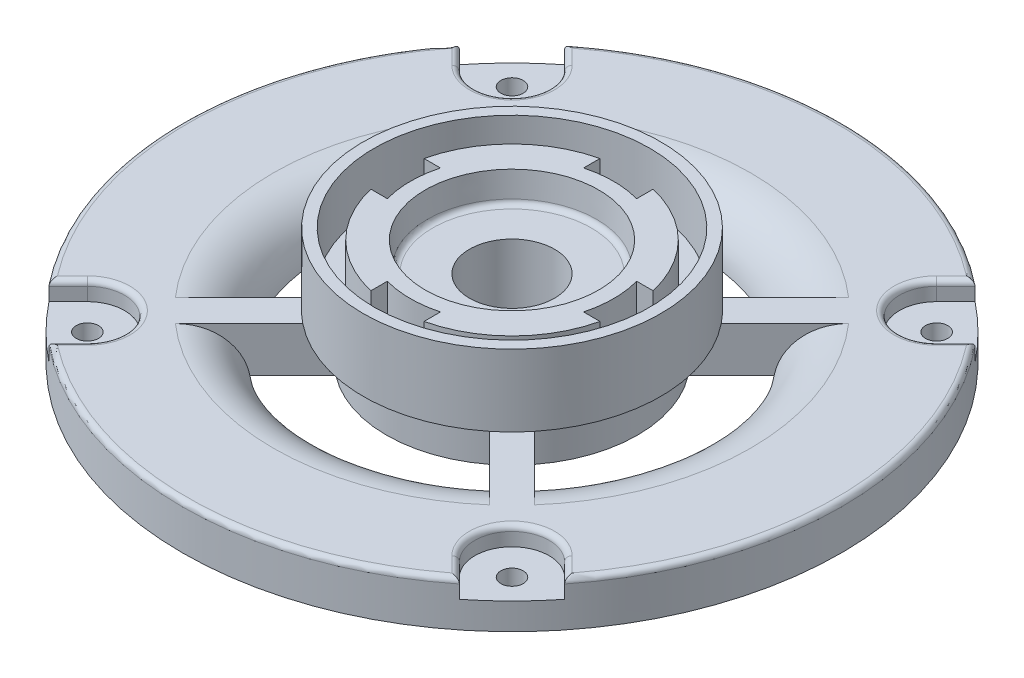
SolidWorks part; units mm, degrees
ref_plane "Спереди" through (0, 0, 0) normal (0, 0, 1) x (1, 0, 0)
ref_plane "Сверху" through (0, 0, 0) normal (0, 1, 0) x (1, 0, 0)
ref_plane "Справа" through (0, 0, 0) normal (1, 0, 0) x (0, 0, -1)
sketch "Эскиз1" plane through (0, 0, 0) normal (0, 1, 0) x (1, 0, 0)
  circle A0 centre (0, 0) radius 62
  circle A1 centre (0, 0) radius 35
  dimension "D1" = 124
  dimension "D2" = 70
extrude "Бобышка-Вытянуть1" add sketch "Эскиз1" along normal blind 8.5
fillet "Скругление1" radius 10 1 edges at (0, 8.5, 35)
sketch "Эскиз2" plane through (0, 8.5, 0) normal (0, 1, 0) x (1, 0, 0)
  line L12 (-14.4488, 18.6915) -> (-29.5475, 33.7902)
  line L16 (-18.6915, 14.4488) -> (-33.7902, 29.5475)
  line L18 (-18.6915, -14.4488) -> (-33.7902, -29.5475)
  line L22 (-14.4488, -18.6915) -> (-29.5475, -33.7902)
  line L24 (14.4488, -18.6915) -> (29.5475, -33.7902)
  line L28 (18.6915, -14.4488) -> (33.7902, -29.5475)
  line L30 (18.6915, 14.4488) -> (33.7902, 29.5475)
  line L34 (14.4488, 18.6915) -> (29.5475, 33.7902)
  arc A1 (29.5475, -33.7902) -> (33.7902, -29.5475) centre (0, 0) ccw
  arc A2 (-33.7902, -29.5475) -> (-29.5475, -33.7902) centre (0, 0) ccw
  arc A3 (-29.5475, 33.7902) -> (-33.7902, 29.5475) centre (0, 0) ccw
  arc A4 (33.7902, 29.5475) -> (29.5475, 33.7902) centre (0, 0) ccw
  arc A5 (14.4488, 18.6915) -> (-14.4488, 18.6915) centre (0, 0) ccw
  arc A6 (-18.6915, 14.4488) -> (-18.6915, -14.4488) centre (0, 0) ccw
  arc A7 (-14.4488, -18.6915) -> (14.4488, -18.6915) centre (0, 0) ccw
  arc A8 (18.6915, -14.4488) -> (18.6915, 14.4488) centre (0, 0) ccw
extrude "Бобышка-Вытянуть2" add sketch "Эскиз2" against normal up to surface (8.5 mm away) up to face at (0, 0, 62)
sketch "Эскиз3" plane through (0, 8.5, 0) normal (0, 1, 0) x (1, 0, 0)
  circle A0 centre (0, 0) radius 28
  dimension "D1" = 56
extrude "Бобышка-Вытянуть3" add sketch "Эскиз3" along normal blind 13.5
sketch "Эскиз4" plane through (0, 22, 0) normal (0, 1, 0) x (1, 0, 0)
  circle A0 centre (0, 0) radius 16.5
  dimension "D1" = 33
extrude "Вырез-Вытянуть1" cut sketch "Эскиз4" against normal blind 7.5 draft 5
fillet "Скругление2" radius 1 1 edges at (0, 14.5, 15.8438)
chamfer "Фаска1" distance 1 angle 45 1 edges at (0, 22, 16.5) first distance on face at (0, 22, 16.5)
sketch "Эскиз5" plane through (0, 14.5, 0) normal (0, 1, 0) x (1, 0, 0)
  circle A0 centre (0, 0) radius 8
  dimension "D1" = 16
extrude "Вырез-Вытянуть2" cut sketch "Эскиз5" against normal through all
sketch "Эскиз6" plane through (0, 22, 0) normal (0, 1, 0) x (1, 0, 0)
  line L5 (-21.5526, -5) -> (-18.4598, -5)
  line L8 (-21.5526, 5) -> (-18.4598, 5)
  line L18 (5, 18.4598) -> (5, 21.5526)
  line L19 (-5, 18.4598) -> (-5, 21.5526)
  line L23 (-5, -18.4598) -> (-5, -21.5526)
  line L25 (5, -18.4598) -> (5, -21.5526)
  line L26 (18.4598, -5) -> (21.5526, -5)
  line L28 (18.4598, 5) -> (21.5526, 5)
  circle A0 centre (0, 0) radius 25.925
  arc A1 (-21.5526, -5) -> (-5, -21.5526) centre (0, 0) ccw
  arc A2 (-5, -18.4598) -> (5, -18.4598) centre (0, 0) ccw
  arc A3 (-5, 21.5526) -> (-21.5526, 5) centre (0, 0) ccw
  arc A4 (21.5526, 5) -> (5, 21.5526) centre (0, 0) ccw
  arc A5 (5, -21.5526) -> (21.5526, -5) centre (0, 0) ccw
  arc A6 (18.4598, -5) -> (18.4598, 5) centre (0, 0) ccw
  arc A7 (5, 18.4598) -> (-5, 18.4598) centre (0, 0) ccw
  arc A8 (-18.4598, 5) -> (-18.4598, -5) centre (0, 0) ccw
  dimension "D1" = 51.85
  dimension "D2" = 44.25
  dimension "D3" = 38.25
extrude "Вырез-Вытянуть3" cut sketch "Эскиз6" against normal blind 10
sketch "Эскиз8" plane through (0, 22, 0) normal (0, 1, 0) x (1, 0, 0)
  circle A0 centre (0, 0) radius 24
extrude "Вырез-Вытянуть4" cut sketch "Эскиз8" against normal blind 2
sketch "Эскиз9" plane through (0, 8.5, 0) normal (0, 1, 0) x (1, 0, 0)
  line L0 (38.6106, 48.5101) -> (35.0018, 44.9013)
  line L1 (48.5101, 38.6106) -> (44.9013, 35.0018)
  line L3 (-38.6106, 48.5101) -> (-35.0018, 44.9013)
  line L5 (-48.5101, 38.6106) -> (-44.9013, 35.0018)
  line L7 (48.5101, -38.6106) -> (44.9013, -35.0018)
  line L8 (38.6106, -48.5101) -> (35.0018, -44.9013)
  line L9 (-38.6106, -48.5101) -> (-35.0018, -44.9013)
  line L10 (-48.5101, -38.6106) -> (-44.9013, -35.0018)
  arc A1 (-38.6106, 48.5101) -> (-48.5101, 38.6106) centre (0, 0) ccw
  arc A2 (-44.9013, 35.0018) -> (-35.0018, 44.9013) centre (-39.9515, 39.9515) ccw
  arc A3 (35.0018, 44.9013) -> (44.9013, 35.0018) centre (39.9515, 39.9515) ccw
  arc A4 (48.5101, 38.6106) -> (38.6106, 48.5101) centre (0, 0) ccw
  arc A5 (44.9013, -35.0018) -> (35.0018, -44.9013) centre (39.9515, -39.9515) ccw
  arc A6 (38.6106, -48.5101) -> (48.5101, -38.6106) centre (0, 0) ccw
  arc A7 (-35.0018, -44.9013) -> (-44.9013, -35.0018) centre (-39.9515, -39.9515) ccw
  arc A8 (-48.5101, -38.6106) -> (-38.6106, -48.5101) centre (0, 0) ccw
  point P26 (0, 0)
  dimension "D1" = 4
extrude "Вырез-Вытянуть5" cut sketch "Эскиз9" against normal blind 3.5
fillet "Скругление3" radius 1 16 edges at (46.7057, 8.5, -36.8062) (35.0018, 8.5, -35.0018) (-46.7057, 8.5, -36.8062) (-35.0018, 8.5, -35.0018) (-36.8062, 8.5, 46.7057) (-35.0018, 8.5, 35.0018) (46.7057, 8.5, 36.8062) (35.0018, 8.5, 35.0018) (36.8062, 8.5, -46.7057) (-36.8062, 8.5, -46.7057) (-46.7057, 8.5, 36.8062) (36.8062, 8.5, 46.7057) (0, 8.5, 62) (62, 8.5, 0) (0, 8.5, -62) (-62, 8.5, 0)
hole_wizard "Отверстие обработанное метчиком M51" positions "Эскиз12" profile "Эскиз13" tap size "M5" standard "ISO"
sketch "Эскиз12" plane through (0, 5, 0) normal (0, 1, 0) x (1, 0, 0)
  point P0 (-39.9515, 39.9515)
  point P3 (39.9515, 39.9515)
  point P6 (39.9515, -39.9515)
  point P9 (-39.9515, -39.9515)
sketch "Эскиз13" plane through (-39.9515, 5, -39.9515) normal (1, 0, 0) x (0, 0, 1)
  line L0 (0, 0) -> (0, 15.2618)
  line L1 (0, 15.2618) -> (2.1, 14)
  line L2 (2.1, 14) -> (2.1, 0)
  line L5 (2.1, 0) -> (0, 0)
  line L10 (0, 15.2618) -> (-2.1, 14) construction
  line L11 (0, -6.35) -> (0, 107.95) construction
  dimension "Диаметр сверла" = 4.2
  dimension "Глубина сверла" = 14
  dimension "Угол заточки сверла" = 118
cosmetic thread "Отверстие резьбы1" parameters "D1"=5, "D2"=5
cosmetic thread "Отверстие резьбы2" parameters "D1"=5, "D2"=5
cosmetic thread "Отверстие резьбы3" parameters "D1"=5, "D2"=5
cosmetic thread "Отверстие резьбы4" parameters "D1"=5, "D2"=5
